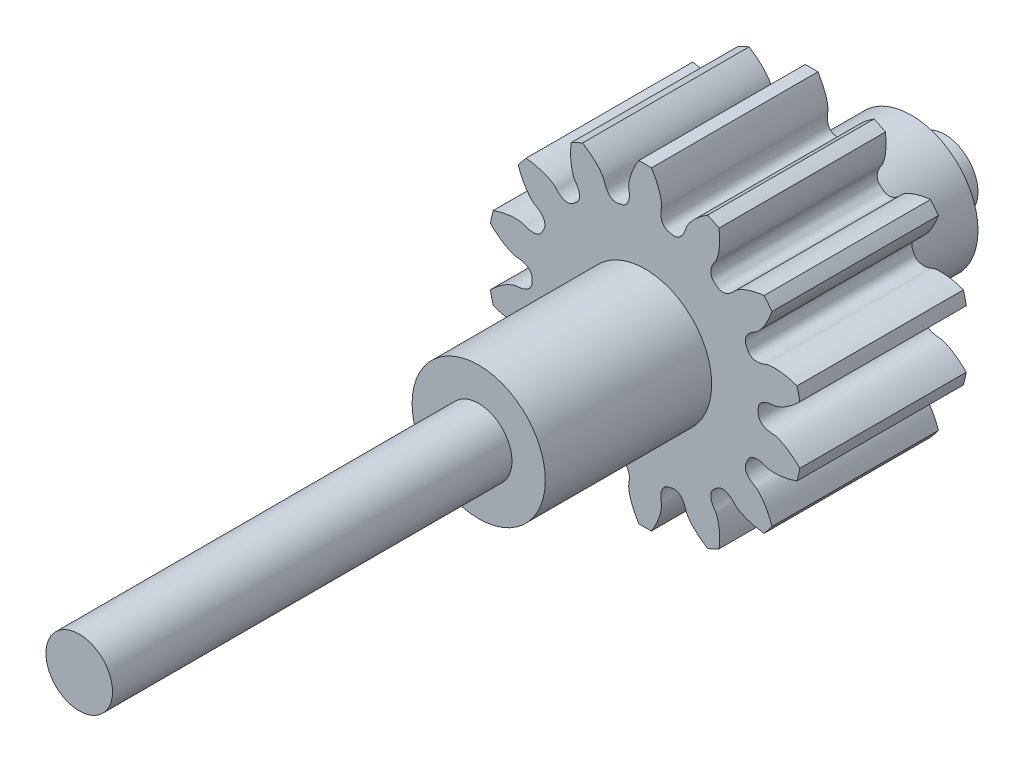
SolidWorks part; units mm, degrees
ref_plane "Alzado" through (0, 0, 0) normal (0, 0, 1) x (1, 0, 0)
ref_plane "Planta" through (0, 0, 0) normal (0, 1, 0) x (1, 0, 0)
ref_plane "Vista lateral" through (0, 0, 0) normal (1, 0, 0) x (0, 0, -1)
ref_axis "Eje1" through (0, 0, 55) along (0, 0, -1)
sketch "SketchRevolveSpur02" plane through (0, 0, 0) normal (1, 0, 0) x (0, 0, -1)
  line L0 (0, 0) -> (1, 0) construction
  line L1 (-0.5, 0) -> (-0.5, 1.1818)
  line L2 (-0.5, 1.1818) -> (0.75, 1.1818)
  line L3 (0.75, 1.1818) -> (0.75, 0)
  line L4 (0.75, 0) -> (-0.5, 0)
  dimension "D1" = 1.25
revolve "Spur02" add sketch "SketchRevolveSpur02" angle 360 about L0
sketch "SketchToothSpur02" plane through (0, 0, 0) normal (0, 0, 1) x (1, 0, 0)
  arc A0 (1.1682, 0.2227) -> (1.1682, -0.2227) centre (0, 0) cw
  spline S0 degree 3 poles (1.1682, -0.2227) (1.1575, -0.2117) (1.1414, -0.1961) (1.1195, -0.1771) (1.104, -0.1645) (1.089, -0.1533) (1.0747, -0.1432) (1.061, -0.1344) (1.048, -0.1266) (1.0358, -0.1199) (1.0245, -0.1142) (1.014, -0.1093) (1.0046, -0.1054) (0.9961, -0.1021) (0.9887, -0.0996) (0.9823, -0.0977) (0.9738, -0.0954) (0.9644, -0.0944) (0.9543, -0.0941) (0.9465, -0.0934) (0.9389, -0.0924) (0.9315, -0.0913) (0.9244, -0.0898) (0.9175, -0.0881) (0.9108, -0.0861) (0.9043, -0.0838) (0.8981, -0.0813) (0.892, -0.0784) (0.8862, -0.0751) (0.8806, -0.0714) (0.8752, -0.0673) (0.87, -0.0627) (0.8651, -0.0575) (0.8606, -0.0516) (0.8566, -0.0449) (0.8533, -0.0376) (0.8508, -0.0295) (0.8496, -0.0218) (0.8491, -0.0119) (0.8497, 0) (0.8491, 0.0119) (0.8496, 0.0218) (0.8508, 0.0295) (0.8533, 0.0376) (0.8566, 0.0449) (0.8606, 0.0516) (0.8651, 0.0575) (0.87, 0.0627) (0.8752, 0.0673) (0.8806, 0.0714) (0.8862, 0.0751) (0.892, 0.0784) (0.8981, 0.0813) (0.9043, 0.0838) (0.9108, 0.0861) (0.9175, 0.0881) (0.9244, 0.0898) (0.9315, 0.0913) (0.9389, 0.0924) (0.9465, 0.0934) (0.9543, 0.0941) (0.9644, 0.0944) (0.9738, 0.0954) (0.9823, 0.0977) (0.9887, 0.0996) (0.9961, 0.1021) (1.0046, 0.1054) (1.014, 0.1093) (1.0245, 0.1142) (1.0358, 0.1199) (1.048, 0.1266) (1.061, 0.1344) (1.0747, 0.1432) (1.089, 0.1533) (1.104, 0.1645) (1.1195, 0.1771) (1.1414, 0.1961) (1.1575, 0.2117) (1.1682, 0.2227) knots 0 0 0 0 0.0554 0.080914 0.104969 0.127567 0.148706 0.168388 0.186612 0.203378 0.218686 0.232536 0.244928 0.255863 0.265339 0.273357 0.279918 0.297272 0.307044 0.316542 0.325781 0.334777 0.343546 0.352112 0.360499 0.368737 0.376863 0.384917 0.39295 0.401018 0.409187 0.41753 0.426123 0.43504 0.444343 0.454063 0.464189 0.474651 0.482386 0.5 0.517614 0.525349 0.535811 0.545937 0.555657 0.56496 0.573877 0.58247 0.590813 0.598982 0.60705 0.615083 0.623137 0.631263 0.639501 0.647888 0.656454 0.665223 0.674219 0.683458 0.692956 0.702728 0.720082 0.726643 0.734661 0.744137 0.755072 0.767464 0.781314 0.796622 0.813388 0.831612 0.851294 0.872433 0.895031 0.919086 0.9446 1 1 1 1
extrude "ToothExtrudeCutSpur02" cut sketch "SketchToothSpur02" against normal up to next and the other way blind 0.5
pattern_circular "PatternSpur02" count 14 every 25.714 about axis through (0, 0, 55) along (0, 0, -1) of "ToothExtrudeCutSpur02"
sketch "AuxiliarySketchSpur02" plane through (0, 0, 0) normal (0, 0, 1) x (1, 0, 0)
  circle A0 centre (0, 0) radius 1.0341 construction
  circle A1 centre (0, 0) radius 0.9717 construction
  circle A2 centre (0, 0) radius 0.977 construction
  circle A3 centre (0, 0) radius 1.1818 construction
  circle A4 centre (0, 0) radius 0.8494 construction
  dimension "PitchDiameter" = 2.0682
  dimension "BaseDiameter" = 1.9435
  dimension "FormDiameter" = 1.9539
  dimension "MajorDiameter" = 2.3636
  dimension "MinorDiameter" = 1.6989
sketch "Croquis1" plane through (0, 0, -0.75) normal (0, 0, -1) x (-1, 0, 0)
  circle A0 centre (0, 0) radius 0.5
  dimension "D1" = 1
extrude "Saliente-Extruir1" add sketch "Croquis1" along normal blind 0.75
sketch "Croquis2" plane through (0, 0, -1.5) normal (0, 0, -1) x (-1, 0, 0)
  circle A0 centre (0, 0) radius 0.25
  dimension "D1" = 0.5
extrude "Saliente-Extruir2" add sketch "Croquis2" along normal blind 0.25
sketch "Croquis3" plane through (0, 0, 0.5) normal (0, 0, 1) x (1, 0, 0)
  circle A0 centre (0, 0) radius 0.5
  dimension "D1" = 1
extrude "Saliente-Extruir3" add sketch "Croquis3" along normal blind 1.25
sketch "Croquis4" plane through (0, 0, 1.75) normal (0, 0, 1) x (1, 0, 0)
  circle A0 centre (0, 0) radius 0.25
  dimension "D1" = 0.5
extrude "Saliente-Extruir4" add sketch "Croquis4" along normal blind 3
